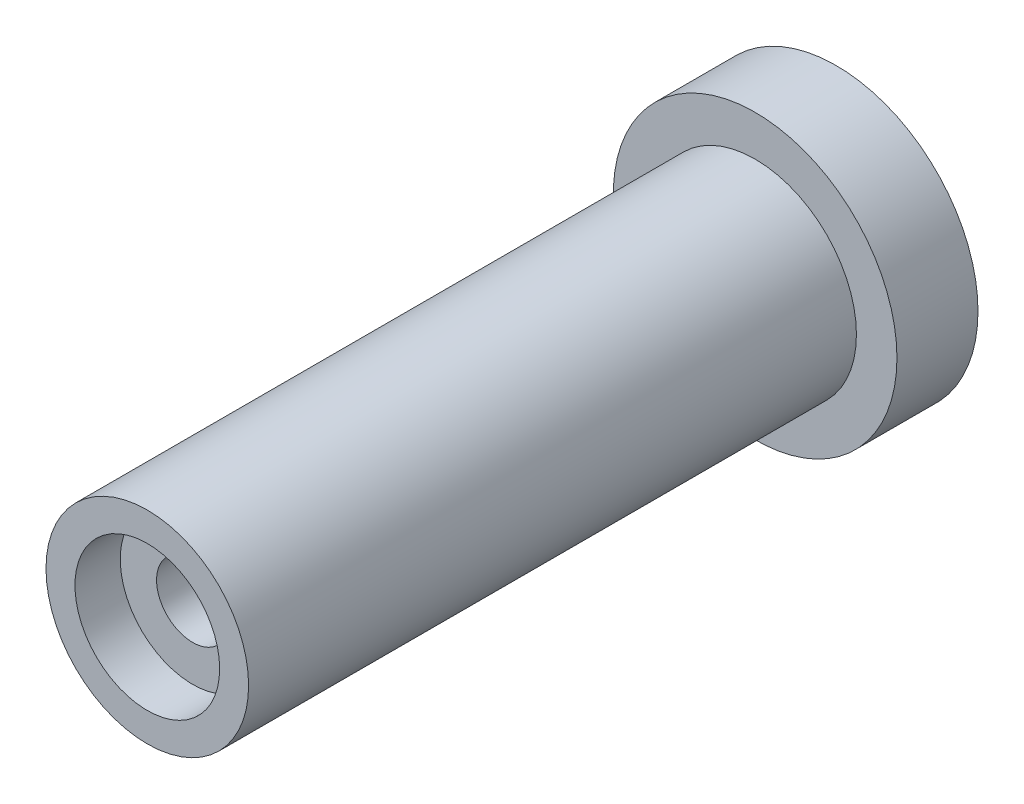
SolidWorks part; units mm, degrees
ref_plane "Plan de face" through (0, 0, 0) normal (0, 0, 1) x (1, 0, 0)
ref_plane "Plan de dessus" through (0, 0, 0) normal (0, 1, 0) x (1, 0, 0)
ref_plane "Plan de droite" through (0, 0, 0) normal (1, 0, 0) x (0, 0, -1)
sketch "Esquisse1" plane through (0, 0, 0) normal (0, 0, 1) x (1, 0, 0)
  circle A0 centre (0, 0) radius 2.5
  dimension "D1" = 5
extrude "Boss.-Extru.1" add sketch "Esquisse1" along normal blind 15
sketch "Esquisse2" plane through (0, 0, 0) normal (0, 0, 1) x (1, 0, 0)
  line L1 (-1.7187, 0.1158) -> (1.7187, 0.1158)
  line L2 (-1.7187, 0.1158) -> (-1.7187, -0.1158)
  line L3 (-1.7187, -0.1158) -> (1.7187, -0.1158)
  line L4 (1.7187, 0.1158) -> (1.7187, -0.1158)
  line L5 (-1.7187, 0.1158) -> (1.7187, -0.1158) construction
  line L6 (-1.7187, -0.1158) -> (1.7187, 0.1158) construction
  line L7 (-0.1158, -1.7187) -> (0.1158, -1.7187)
  line L8 (-0.1158, -1.7187) -> (-0.1158, 1.7187)
  line L9 (-0.1158, 1.7187) -> (0.1158, 1.7187)
  line L10 (0.1158, -1.7187) -> (0.1158, 1.7187)
  line L11 (-0.1158, -1.7187) -> (0.1158, 1.7187) construction
  line L12 (-0.1158, 1.7187) -> (0.1158, -1.7187) construction
  circle A0 centre (0, 0) radius 3.5
  dimension "D1" = 7
extrude "Boss.-Extru.2" add sketch "Esquisse2" against normal blind 2 contours A0 L10 L7 L8 L3 L2 L1 L9 L4 region at (-3.401, 0, 0)
hole_wizard "Chambrage pour vis à tête ronde bombée #01" positions "Esquisse19" profile "Esquisse17" counterbore size "#0" standard "Ansi Inch"
sketch "Esquisse19" plane through (0, 0, 15) normal (0, 0, 1) x (1, 0, 0)
  point P0 (0, 0)
sketch "Esquisse17" plane through (0, 0, 15) normal (1, 0, 0) x (0, -1, 0)
  line L0 (0, 0) -> (0, 6.5342)
  line L1 (0, 6.5342) -> (0.889, 6)
  line L2 (0.889, 6) -> (0.889, 1.1176)
  line L3 (0.889, 1.1176) -> (1.7856, 1.1176)
  line L4 (1.7856, 1.1176) -> (1.7856, 0)
  line L5 (1.7856, 0) -> (0, 0)
  line L10 (0, 6.5342) -> (-0.889, 6) construction
  line L11 (0, -6.35) -> (0, 107.95) construction
  dimension "Diamètre du perçage" = 1.778
  dimension "Profondeur du perçage" = 6
  dimension "Diamètre du chambrage" = 3.5712
  dimension "Profondeur du chambrage" = 1.1176
  dimension "Angle de pointe" = 118
